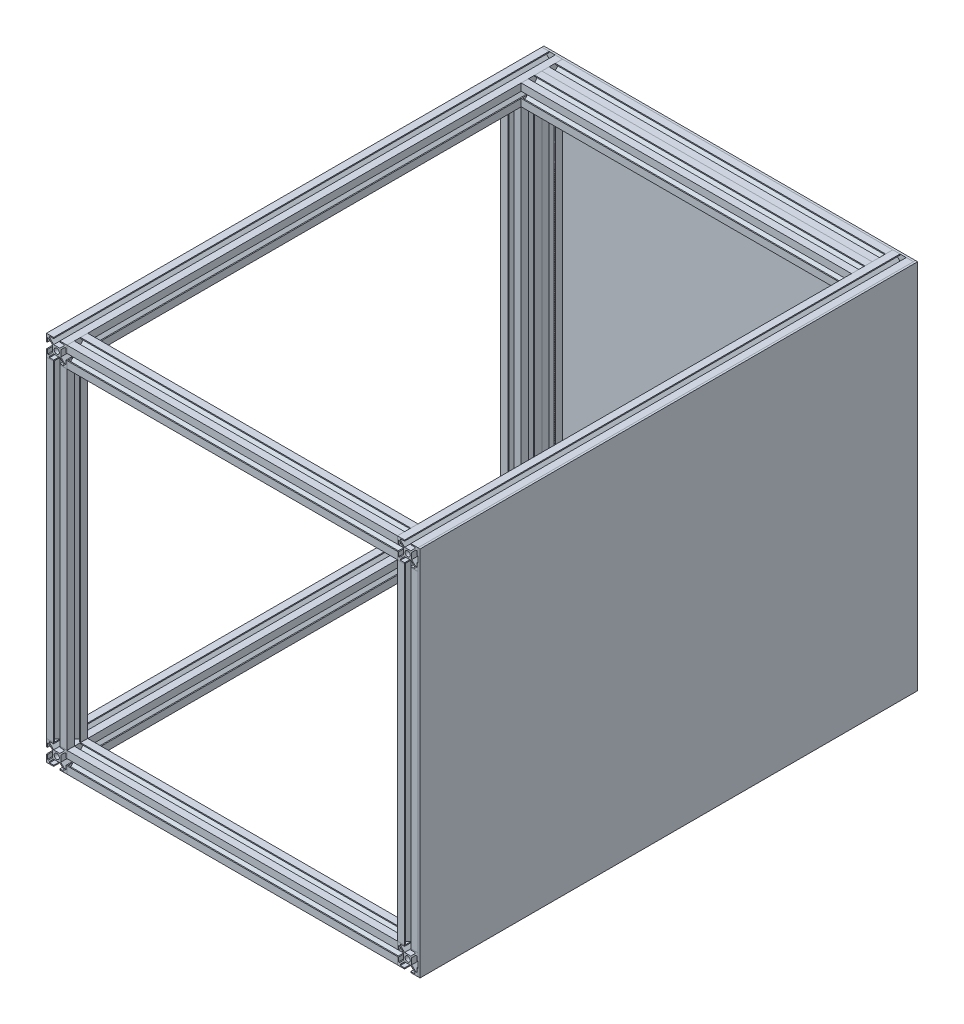
SolidWorks part; units mm, degrees
material "6063-T1"
ref_plane "Front Plane" through (0, 0, 0) normal (1, 0, 0) x (0, 1, 0)
ref_plane "Top Plane" through (0, 0, 0) normal (0, 0, 1) x (0, 1, 0)
ref_plane "Right Plane" through (0, 0, 0) normal (0, 1, 0) x (-1, 0, 0)
ref_axis "Axis1" through (0, 0, 0) along (0, 0, 1)
sketch "Sketch2" plane through (0, 0, 0) normal (1, 0, 0) x (0, 1, 0)
  line L5 (-180, 3) -> (-180, 10)
  line L67 (-180, 10) -> (-160, 10) construction
  line L68 (-180, 10) -> (-180, -10) construction
  line L69 (-180, -10) -> (-160, -10) construction
  line L70 (-160, 10) -> (-160, -10) construction
  line L72 (-160, 0) -> (160, 0) construction
  line L73 (-180, 10) -> (-173, 10)
  line L74 (-173, 10) -> (-173, 9)
  line L75 (-173, 9) -> (-177, 9)
  line L76 (-177, 9) -> (-177, 7.9857)
  line L77 (-177, 7.9857) -> (-173, 3.9857)
  line L78 (-173, 3.9857) -> (-170, 3.9857)
  line L79 (-180, 3) -> (-179, 3)
  line L80 (-179, 3) -> (-179, 7)
  line L81 (-179, 7) -> (-177.9857, 7)
  line L82 (-177.9857, 7) -> (-173.9857, 3)
  line L83 (-173.9857, 3) -> (-173.9857, 0)
  line L84 (-173.9857, 3) -> (-173, 3.9857) construction
  line L85 (-167, 10) -> (-160, 10)
  line L86 (-160, 10) -> (-160, 3)
  line L87 (-160, 3) -> (-161, 3)
  line L88 (-161, 3) -> (-161, 7)
  line L89 (-161, 7) -> (-162.0143, 7)
  line L90 (-162.0143, 7) -> (-166.0143, 3)
  line L91 (-166.0143, 3) -> (-166.0143, 0)
  line L92 (-167, 10) -> (-167, 9)
  line L93 (-167, 9) -> (-163, 9)
  line L94 (-163, 9) -> (-163, 7.9857)
  line L95 (-163, 7.9857) -> (-167, 3.9857)
  line L96 (-167, 3.9857) -> (-170, 3.9857)
  line L97 (-167, 3.9857) -> (-166.0143, 3) construction
  line L98 (-160, -3) -> (-160, -10)
  line L99 (-160, -10) -> (-167, -10)
  line L100 (-167, -10) -> (-167, -9)
  line L101 (-167, -9) -> (-163, -9)
  line L102 (-163, -9) -> (-163, -7.9857)
  line L103 (-163, -7.9857) -> (-167, -3.9857)
  line L104 (-167, -3.9857) -> (-170, -3.9857)
  line L105 (-160, -3) -> (-161, -3)
  line L106 (-161, -3) -> (-161, -7)
  line L107 (-161, -7) -> (-162.0143, -7)
  line L108 (-162.0143, -7) -> (-166.0143, -3)
  line L109 (-166.0143, -3) -> (-166.0143, 0)
  line L110 (-166.0143, -3) -> (-167, -3.9857) construction
  line L111 (-173, -10) -> (-180, -10)
  line L112 (-180, -10) -> (-180, -3)
  line L113 (-180, -3) -> (-179, -3)
  line L114 (-179, -3) -> (-179, -7)
  line L115 (-179, -7) -> (-177.9857, -7)
  line L116 (-177.9857, -7) -> (-173.9857, -3)
  line L117 (-173.9857, -3) -> (-173.9857, 0)
  line L118 (-173, -10) -> (-173, -9)
  line L119 (-173, -9) -> (-177, -9)
  line L120 (-177, -9) -> (-177, -7.9857)
  line L121 (-177, -7.9857) -> (-173, -3.9857)
  line L122 (-173, -3.9857) -> (-170, -3.9857)
  line L123 (-173, -3.9857) -> (-173.9857, -3) construction
  circle A0 centre (-170, 0) radius 2.5
  point P0 (-192.5803, 22.4509)
  point P72 (-160, 0)
  point P107 (-170, 0)
  dimension "D5" = 5
  dimension "D1" = 20
  dimension "D2" = 45
  dimension "D4" = 6
  dimension "D3" = 14
  dimension "D8" = 45
  dimension "D7" = 1
  dimension "D6" = 4
sketch "Sketch1" plane through (0, 0, 0) normal (0, 0, 1) x (0, 1, 0)
  line L0 (-160, 160) -> (160, -160) construction
  line L5 (-160, 160) -> (160, 160)
  line L6 (-160, 160) -> (-160, -160)
  line L7 (-160, -160) -> (160, -160)
  line L8 (160, 160) -> (160, -160)
  point P108 (0, 0)
  dimension "D1" = 320
  dimension "D2" = 320
sweep "Aluminium Extrsion Base" add profiles "Sketch2" path "Sketch1"
pattern_circular "CirPattern1" count 4 over 360 about axis through (0, 0, 0) along (0, 0, 1) of "Aluminium Extrsion Base"
mirror "Mirror5" about plane through (-160, 167, 10) normal (0, 0, -1) of bodies 122 118 124 123
sketch "Sketch4" plane through (0, 0, -10) normal (0, 0, 1) x (0, 1, 0)
  line L5 (-180, -167) -> (-180, -160)
  line L67 (-180, -160) -> (-160, -160) construction
  line L68 (-180, -160) -> (-180, -180) construction
  line L69 (-180, -180) -> (-160, -180) construction
  line L70 (-160, -160) -> (-160, -180) construction
  line L71 (-160, -167) -> (-160, -170) construction
  line L73 (-180, -160) -> (-173, -160)
  line L74 (-173, -160) -> (-173, -161)
  line L75 (-173, -161) -> (-177, -161)
  line L76 (-177, -161) -> (-177, -162.0896)
  line L77 (-177, -162.0896) -> (-173, -166.0896)
  line L78 (-173, -166.0896) -> (-170, -166.0896)
  line L79 (-180, -167) -> (-179, -167)
  line L80 (-179, -167) -> (-179, -163)
  line L81 (-179, -163) -> (-177.9104, -163)
  line L82 (-177.9104, -163) -> (-173.9104, -167)
  line L83 (-173.9104, -167) -> (-173.9104, -170)
  line L84 (-173.9104, -167) -> (-173, -166.0896) construction
  line L85 (-167, -160) -> (-160, -160)
  line L86 (-160, -160) -> (-160, -167)
  line L87 (-160, -167) -> (-161, -167)
  line L88 (-161, -167) -> (-161, -163)
  line L89 (-161, -163) -> (-162.0896, -163)
  line L90 (-162.0896, -163) -> (-166.0896, -167)
  line L91 (-166.0896, -167) -> (-166.0896, -170)
  line L92 (-167, -160) -> (-167, -161)
  line L93 (-167, -161) -> (-163, -161)
  line L94 (-163, -161) -> (-163, -162.0896)
  line L95 (-163, -162.0896) -> (-167, -166.0896)
  line L96 (-167, -166.0896) -> (-170, -166.0896)
  line L97 (-167, -166.0896) -> (-166.0896, -167) construction
  line L98 (-160, -173) -> (-160, -180)
  line L99 (-160, -180) -> (-167, -180)
  line L100 (-167, -180) -> (-167, -179)
  line L101 (-167, -179) -> (-163, -179)
  line L102 (-163, -179) -> (-163, -177.9104)
  line L103 (-163, -177.9104) -> (-167, -173.9104)
  line L104 (-167, -173.9104) -> (-170, -173.9104)
  line L105 (-160, -173) -> (-161, -173)
  line L106 (-161, -173) -> (-161, -177)
  line L107 (-161, -177) -> (-162.0896, -177)
  line L108 (-162.0896, -177) -> (-166.0896, -173)
  line L109 (-166.0896, -173) -> (-166.0896, -170)
  line L110 (-166.0896, -173) -> (-167, -173.9104) construction
  line L111 (-173, -180) -> (-180, -180)
  line L112 (-180, -180) -> (-180, -173)
  line L113 (-180, -173) -> (-179, -173)
  line L114 (-179, -173) -> (-179, -177)
  line L115 (-179, -177) -> (-177.9104, -177)
  line L116 (-177.9104, -177) -> (-173.9104, -173)
  line L117 (-173.9104, -173) -> (-173.9104, -170)
  line L118 (-173, -180) -> (-173, -179)
  line L119 (-173, -179) -> (-177, -179)
  line L120 (-177, -179) -> (-177, -177.9104)
  line L121 (-177, -177.9104) -> (-173, -173.9104)
  line L122 (-173, -173.9104) -> (-170, -173.9104)
  line L123 (-173, -173.9104) -> (-173.9104, -173) construction
  line L124 (-167, -160) -> (-170, -160) construction
  circle A0 centre (-170, -170) radius 2.5
  point P0 (-192.5803, 22.4509)
  point P72 (-160, -170)
  point P107 (-170, -170)
  dimension "D2" = 45
  dimension "D5" = 5
  dimension "D1" = 20
  dimension "D3" = 14
  dimension "D4" = 6
  dimension "D7" = 1
  dimension "D8" = 45
  dimension "D6" = 4
extrude "Aluminium Extrusion Pillar" add sketch "Sketch4" along normal blind 480 separate body
pattern_circular "CirPattern2" count 4 over 360 about axis through (0, 0, 0) along (0, 0, 1) of bodies 125
ref_plane "Plane2" through (0, 0, 230) normal (0, 0, 1) x (1, 0, 0)
mirror "Mirror4" about plane through (0, 0, 230) normal (0, 0, 1) of bodies 124 118 122 123
sketch "Sketch5" plane through (0, 0, -10) normal (0, 0, -1) x (1, 0, 0)
  line L1 (-180, 180) -> (180, 180)
  line L2 (-180, 180) -> (-180, -180)
  line L3 (-180, -180) -> (180, -180)
  line L4 (180, 180) -> (180, -180)
  line L5 (0, -180) -> (0, 180) construction
  line L6 (-180, 0) -> (180, 0) construction
  circle A0 centre (-170, -170) radius 2.5 construction
  circle A1 centre (170, -170) radius 2.5 construction
  circle A2 centre (170, 170) radius 2.5 construction
  circle A3 centre (-170, 170) radius 2.5 construction
  circle A4 centre (-170, -170) radius 2.5
  circle A5 centre (170, -170) radius 2.5
  circle A6 centre (170, 170) radius 2.5
  circle A7 centre (-170, 170) radius 2.5
  point P308 (0, 0)
extrude "Bottom Plate" add sketch "Sketch5" along normal blind 2 separate body
sketch "Sketch6" plane through (180, 0, 0) normal (1, 0, 0) x (0, 1, 0)
  line L1 (-180, 470) -> (180, 470)
  line L2 (-180, 470) -> (-180, -12)
  line L3 (-180, -12) -> (180, -12)
  line L4 (180, 470) -> (180, -12)
  line L5 (0, -12) -> (0, 470) construction
  line L6 (-180, 229) -> (180, 229) construction
  point P96 (0, 229)
extrude "Back Plate" add sketch "Sketch6" along normal blind 2 separate body
equation "\"extrusion_width\"= 20mm"
equation "\"frame_height\"= 440mm"
equation "\"frame_width\"= 320mm"
equation "\"frame_length\"= 320mm"
equation "\"bed_radius\"= 100mm"
equation "\"bottom_plate_thickness\"=2"
equation "\"D2@Sketch1\"=\"frame_length\""
equation "\"D1@Sketch1\"=\"frame_width\""
equation "\"D1@Sketch2\"=\"extrusion_width\""
equation "\"D1@Aluminium Extrusion Pillar\" = \"frame_height\" + \"extrusion_width\" * 2"
equation "\"D1@Bottom Plate\" = \"bottom_plate_thickness\""
